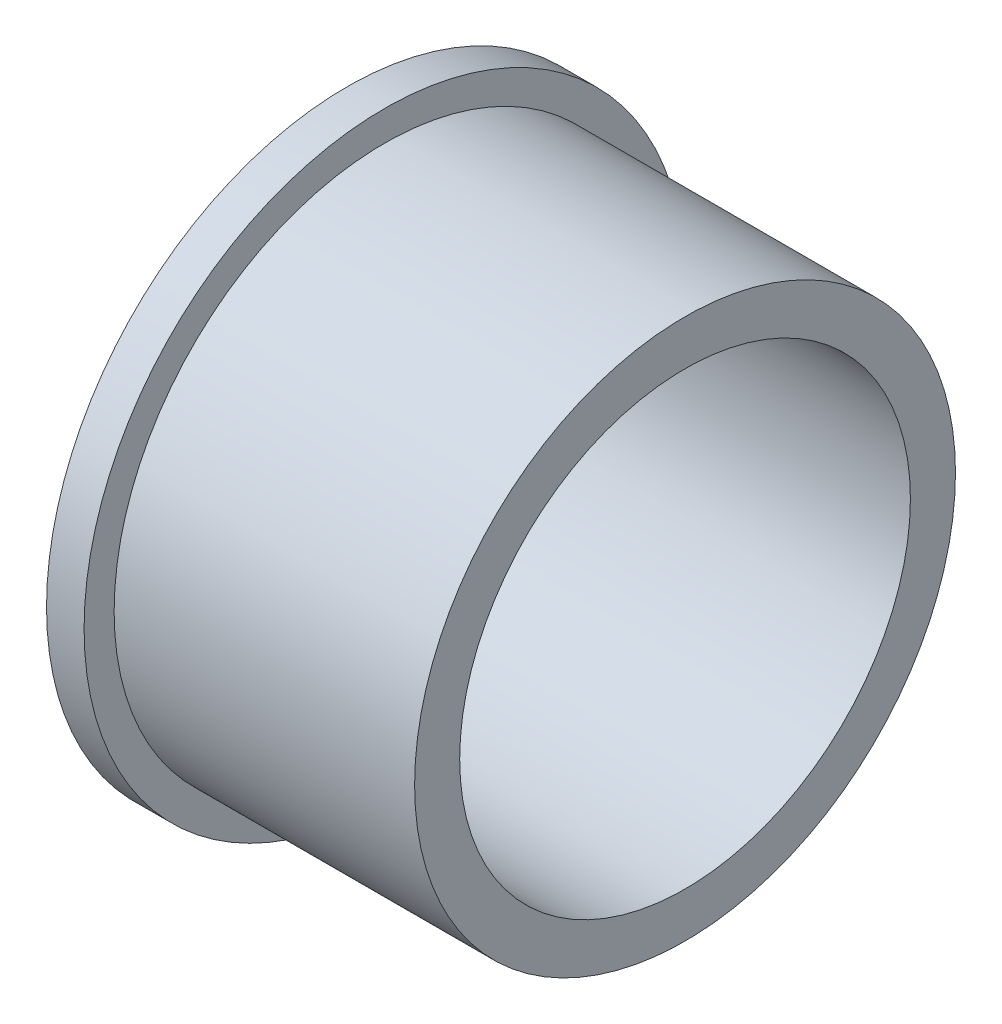
SolidWorks part; units mm, degrees
material "Brass"
ref_plane "Front" through (0, 0, 0) normal (0, 0, 1) x (1, 0, 0)
ref_plane "Top" through (0, 0, 0) normal (0, 1, 0) x (1, 0, 0)
ref_plane "Right" through (0, 0, 0) normal (1, 0, 0) x (0, 0, -1)
ref_axis "Axis1" through (-84.4107, 0, 0) along (1, 0, 0)
ref_axis "Axis2" through (0, 64.3378, 0) along (0, -1, 0)
ref_axis "Axis3" through (0, 0, -102.329) along (0, 0, 1)
sketch "Sketch1" plane through (0, 0, 0) normal (0, 0, 1) x (1, 0, 0)
  line L0 (0, 20) -> (0, 15)
  line L1 (0, 15) -> (22.5, 15)
  line L2 (22.5, 15) -> (22.5, 18)
  line L3 (22.5, 18) -> (2.5, 18)
  line L4 (2.5, 18) -> (2.5, 20)
  line L5 (2.5, 20) -> (0, 20)
  dimension "D1" = 15
  dimension "D2" = 20
  dimension "D3" = 20
  dimension "D4" = 22.5
  dimension "D5" = 18
revolve "Revolve1" add sketch "Sketch1" angle 360 about axis through (-84.4107, 0, 0) along (1, 0, 0)
